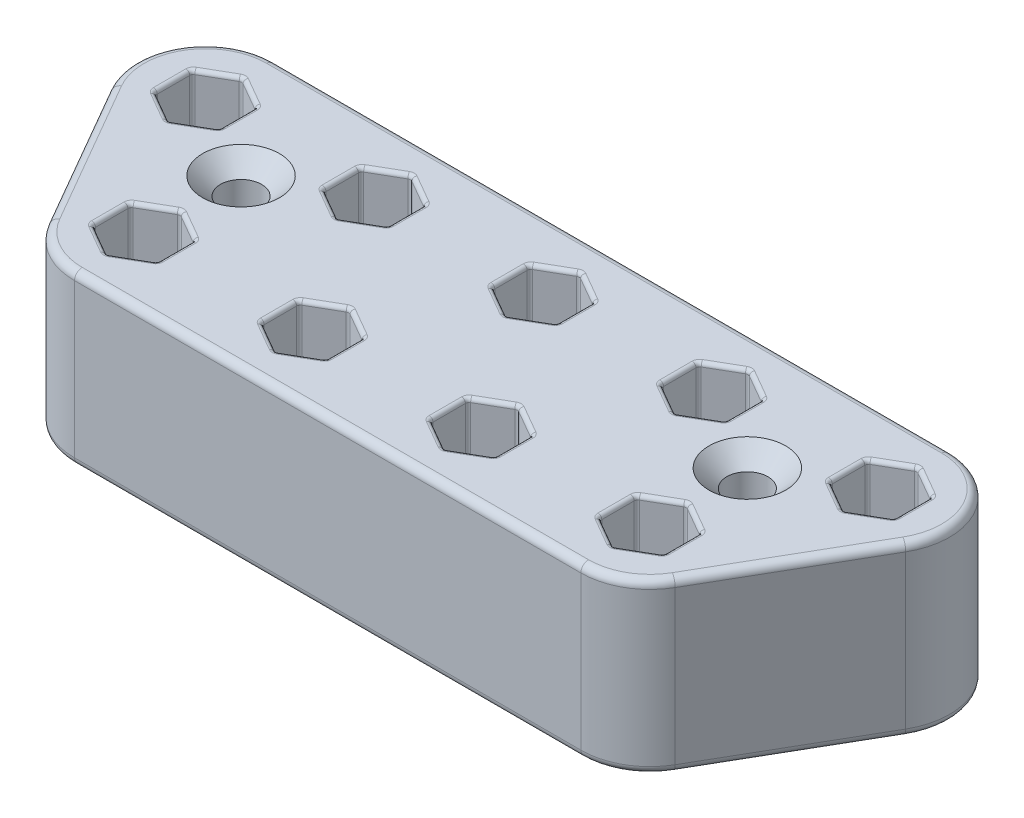
SolidWorks part; units mm, degrees
ref_plane "Front Plane" through (0, 0, 0) normal (0, 0, 1) x (1, 0, 0)
ref_plane "Top Plane" through (0, 0, 0) normal (0, 1, 0) x (1, 0, 0)
ref_plane "Right Plane" through (0, 0, 0) normal (1, 0, 0) x (0, 0, -1)
sketch "Sketch1" plane through (0, 0, 0) normal (0, 1, 0) x (1, 0, 0)
  line L1 (3.302, 1.9064) -> (0, 3.8128)
  line L2 (0, 3.8128) -> (-3.302, 1.9064)
  line L3 (-3.302, 1.9064) -> (-3.302, -1.9064)
  line L4 (-3.302, -1.9064) -> (0, -3.8128)
  line L5 (0, -3.8128) -> (3.302, -1.9064)
  line L6 (3.302, -1.9064) -> (3.302, 1.9064)
  line L7 (8.7313, 5.041) -> (0, 10.082)
  line L8 (0, 10.082) -> (-8.7312, 5.041)
  line L9 (-8.7312, 5.041) -> (-8.7312, -5.041)
  line L10 (-8.7312, -5.041) -> (0, -10.082)
  line L11 (0, -10.082) -> (8.7313, -5.041)
  line L12 (8.7313, -5.041) -> (8.7313, 5.041)
  circle A0 centre (0, 0) radius 3.302 construction
  circle A1 centre (0, 0) radius 8.7312 construction
  dimension "D2" = 17.4625
  dimension "D1" = 6.604
extrude "Boss-Extrude1" add sketch "Sketch1" along normal blind 15.875
sketch "Sketch3" plane through (0, 0, 0) normal (0, -1, 0) x (1, 0, 0)
  line L6 (8.7313, -5.041) -> (8.7313, 5.041)
  line L7 (8.7313, 5.041) -> (0, 10.082)
  line L8 (0, 10.082) -> (-8.7312, 5.041)
  line L9 (-8.7312, 5.041) -> (-8.7312, -5.041)
  line L10 (-8.7312, -5.041) -> (0, -10.082)
  line L11 (0, -10.082) -> (8.7313, -5.041)
  line L12 (8.7313, -5.041) -> (8.7313, 5.041)
  line L13 (8.7313, 5.041) -> (0, 10.082)
  line L14 (0, 10.082) -> (-8.7312, 5.041)
  line L15 (-8.7312, 5.041) -> (-8.7312, -5.041)
  line L16 (-8.7312, -5.041) -> (0, -10.082)
  line L17 (0, -10.082) -> (8.7313, -5.041)
  dimension "D1" = 0
extrude "Boss-Extrude3" add sketch "Sketch3" along normal blind 1.5875
fillet "Fillet1" radius 0.3969 18 edges at (0, 7.9375, 3.8128) (1.651, 0, 2.8596) (-1.651, 0, 2.8596) (-1.651, 15.875, 2.8596) (-3.302, 7.9375, 1.9064) (3.302, 7.9375, 1.9064) (1.651, 15.875, 2.8596) (3.302, 0, 0) (-3.302, 0, 0) (-3.302, 15.875, 0) (-3.302, 7.9375, -1.9064) (3.302, 7.9375, -1.9064) (3.302, 15.875, 0) (1.651, 0, -2.8596) (-1.651, 0, -2.8596) (-1.651, 15.875, -2.8596) (1.651, 15.875, -2.8596) (0, 7.9375, -3.8128)
pattern_linear "LPattern1" count 5 spacing 17.4625 along (1, 0, 0) count 2 spacing 17.4625 along (0.5, 0, 0.866) skipping (4, 1) of "Boss-Extrude1", "Boss-Extrude3", "Fillet1"
sketch "Sketch5" plane through (0, -1.5875, 0) normal (0, -1, 0) x (1, 0, 0)
  line L48 (0, 20.164) -> (0, 10.082)
  line L49 (0, 10.082) -> (-8.7312, 5.041)
  line L50 (-8.7312, 5.041) -> (-8.7312, -5.041)
  line L51 (-8.7312, -5.041) -> (0, -10.082)
  line L52 (0, -10.082) -> (8.7312, -5.041)
  line L53 (8.7312, -5.041) -> (17.4625, -10.082)
  line L54 (17.4625, -10.082) -> (26.1938, -5.041)
  line L55 (26.1938, -5.041) -> (34.925, -10.082)
  line L56 (34.925, -10.082) -> (43.6562, -5.041)
  line L57 (43.6562, -5.041) -> (52.3875, -10.082)
  line L58 (52.3875, -10.082) -> (61.1187, -5.041)
  line L59 (61.1187, -5.041) -> (69.85, -10.082)
  line L60 (69.85, -10.082) -> (78.5813, -5.041)
  line L61 (78.5813, -5.041) -> (78.5813, 5.041)
  line L62 (78.5813, 5.041) -> (69.85, 10.082)
  line L63 (69.85, 10.082) -> (69.85, 20.164)
  line L64 (69.85, 20.164) -> (61.1188, 25.2049)
  line L65 (61.1188, 25.2049) -> (52.3875, 20.164)
  line L66 (52.3875, 20.164) -> (43.6563, 25.2049)
  line L67 (43.6563, 25.2049) -> (34.925, 20.164)
  line L68 (34.925, 20.164) -> (26.1938, 25.2049)
  line L69 (26.1938, 25.2049) -> (17.4625, 20.164)
  line L70 (17.4625, 20.164) -> (8.7313, 25.2049)
  line L71 (8.7313, 25.2049) -> (0, 20.164)
  line L72 (0, 20.164) -> (0, 10.082)
  line L73 (0, 10.082) -> (-8.7312, 5.041)
  line L74 (-8.7312, 5.041) -> (-8.7312, -5.041)
  line L75 (-8.7312, -5.041) -> (0, -10.082)
  line L76 (0, -10.082) -> (8.7312, -5.041)
  line L77 (8.7312, -5.041) -> (17.4625, -10.082)
  line L78 (17.4625, -10.082) -> (26.1938, -5.041)
  line L79 (26.1938, -5.041) -> (34.925, -10.082)
  line L80 (34.925, -10.082) -> (43.6562, -5.041)
  line L81 (43.6562, -5.041) -> (52.3875, -10.082)
  line L82 (52.3875, -10.082) -> (61.1187, -5.041)
  line L83 (61.1187, -5.041) -> (69.85, -10.082)
  line L84 (69.85, -10.082) -> (78.5813, -5.041)
  line L85 (78.5813, -5.041) -> (78.5813, 5.041)
  line L86 (78.5813, 5.041) -> (69.85, 10.082)
  line L87 (69.85, 10.082) -> (69.85, 20.164)
  line L88 (69.85, 20.164) -> (61.1188, 25.2049)
  line L89 (61.1188, 25.2049) -> (52.3875, 20.164)
  line L90 (52.3875, 20.164) -> (43.6563, 25.2049)
  line L91 (43.6563, 25.2049) -> (34.925, 20.164)
  line L92 (34.925, 20.164) -> (26.1938, 25.2049)
  line L93 (26.1938, 25.2049) -> (17.4625, 20.164)
  line L94 (17.4625, 20.164) -> (8.7313, 25.2049)
  line L95 (8.7313, 25.2049) -> (0, 20.164)
  line L120 (-6.35, 23.8301) -> (-6.35, 13.7482)
  line L121 (-6.35, 13.7482) -> (-15.0812, 8.7072)
  line L122 (-15.0812, 8.7072) -> (-15.0812, -8.7072)
  line L123 (-15.0812, -8.7072) -> (0, -17.4143)
  line L124 (0, -17.4143) -> (8.7312, -12.3733)
  line L125 (8.7312, -12.3733) -> (17.4625, -17.4143)
  line L126 (17.4625, -17.4143) -> (26.1938, -12.3733)
  line L127 (26.1938, -12.3733) -> (34.925, -17.4143)
  line L128 (34.925, -17.4143) -> (43.6562, -12.3733)
  line L129 (43.6562, -12.3733) -> (52.3875, -17.4143)
  line L130 (52.3875, -17.4143) -> (61.1187, -12.3733)
  line L131 (61.1187, -12.3733) -> (69.85, -17.4143)
  line L132 (69.85, -17.4143) -> (84.9313, -8.7072)
  line L133 (84.9313, -8.7072) -> (84.9313, 8.7072)
  line L134 (84.9313, 8.7072) -> (76.2, 13.7482)
  line L135 (76.2, 13.7482) -> (76.2, 23.8301)
  line L136 (76.2, 23.8301) -> (61.1188, 32.5373)
  line L137 (61.1188, 32.5373) -> (52.3875, 27.4963)
  line L138 (52.3875, 27.4963) -> (43.6563, 32.5373)
  line L139 (43.6563, 32.5373) -> (34.925, 27.4963)
  line L140 (34.925, 27.4963) -> (26.1938, 32.5373)
  line L141 (26.1938, 32.5373) -> (17.4625, 27.4963)
  line L142 (17.4625, 27.4963) -> (8.7313, 32.5373)
  line L143 (8.7313, 32.5373) -> (-6.35, 23.8301)
  line L144 (-6.35, 23.8301) -> (-6.35, 13.7482)
  line L145 (-6.35, 13.7482) -> (-15.0812, 8.7072)
  line L146 (-15.0812, 8.7072) -> (-15.0812, -8.7072)
  line L147 (-15.0812, -8.7072) -> (0, -17.4143)
  line L148 (0, -17.4143) -> (8.7312, -12.3733)
  line L149 (8.7312, -12.3733) -> (17.4625, -17.4143)
  line L150 (17.4625, -17.4143) -> (26.1938, -12.3733)
  line L151 (26.1938, -12.3733) -> (34.925, -17.4143)
  line L152 (34.925, -17.4143) -> (43.6562, -12.3733)
  line L153 (43.6562, -12.3733) -> (52.3875, -17.4143)
  line L154 (52.3875, -17.4143) -> (61.1187, -12.3733)
  line L155 (61.1187, -12.3733) -> (69.85, -17.4143)
  line L156 (69.85, -17.4143) -> (84.9313, -8.7072)
  line L157 (84.9313, -8.7072) -> (84.9313, 8.7072)
  line L158 (84.9313, 8.7072) -> (76.2, 13.7482)
  line L159 (76.2, 13.7482) -> (76.2, 23.8301)
  line L160 (76.2, 23.8301) -> (61.1188, 32.5373)
  line L161 (61.1188, 32.5373) -> (52.3875, 27.4963)
  line L162 (52.3875, 27.4963) -> (43.6563, 32.5373)
  line L163 (43.6563, 32.5373) -> (34.925, 27.4963)
  line L164 (34.925, 27.4963) -> (26.1938, 32.5373)
  line L165 (26.1938, 32.5373) -> (17.4625, 27.4963)
  line L166 (17.4625, 27.4963) -> (8.7313, 32.5373)
  line L167 (8.7313, 32.5373) -> (-6.35, 23.8301)
  dimension "D1" = 0
  dimension "D2" = 6.35
extrude "Boss-Extrude4" add sketch "Sketch5" against normal up to surface (17.4625 mm away) up to face at (69.85, 15.875, 0)
sketch "Sketch4" plane through (0, 15.875, 0) normal (0, 1, 0) x (1, 0, 0)
  line L0 (0, 0) -> (8.7313, -15.123) construction
  line L1 (8.7313, -15.123) -> (61.1187, -15.123) construction
  line L2 (61.1187, -15.123) -> (69.85, 0) construction
  line L3 (69.85, 0) -> (0, 0) construction
  line L5 (-12.3733, 7.1437) -> (4.6068, -22.2667)
  line L6 (4.6068, -22.2667) -> (65.2432, -22.2667)
  line L7 (65.2432, -22.2667) -> (82.2233, 7.1437)
  line L8 (82.2233, 7.1437) -> (-12.3733, 7.1437)
  line L9 (-3.1036, 2.021) -> (-0.1984, 3.6983) construction
  point P3 (59.7318, -14.2324)
  dimension "D2" = 17.4625
  dimension "D1" = 69.85
  dimension "D3" = 7.1437
extrude "Cut-Extrude1" cut sketch "Sketch4" against normal through all both and the other way through all flip side to cut
fillet "Fillet2" radius 7.1437 4 edges at (82.2233, 7.1438, -7.1437) (65.2432, 7.1438, 22.2667) (4.6068, 7.1438, 22.2667) (-12.3733, 7.1437, -7.1437)
fillet "Fillet3" radius 0.7937 16 edges at (-1.821, -1.5875, 11.1334) (5.1594, -1.5875, 21.3096) (34.925, -1.5875, 22.2667) (64.6906, -1.5875, 21.3096) (71.671, -1.5875, 11.1334) (76.0367, -1.5875, -3.5719) (34.925, -1.5875, -7.1437) (34.925, 15.875, -7.1437) (76.0367, 15.875, -3.5719) (71.671, 15.875, 11.1334) (64.6906, 15.875, 21.3096) (34.925, 15.875, 22.2667) (5.1594, 15.875, 21.3096) (-1.821, 15.875, 11.1334) (-6.1867, -1.5875, -3.5719) (-6.1867, 15.875, -3.5719)
sketch "Sketch6" plane through (0, 0, 0) normal (0, 1, 0) x (1, 0, 0)
  circle A0 centre (8.7312, -5.041) radius 6.7274 construction
  point P11 (8.7312, -5.041)
ref_axis "Axis1" through (8.7312, 0, 5.041) along (0, 1, 0)
ref_plane "Plane1" through (8.7312, 0, 0) normal (1, 0, 0) x (0, 1, 0)
sketch "Sketch7" plane through (8.7312, 0, 0) normal (1, 0, 0) x (0, 1, 0)
  line L0 (-1.5875, 5.041) -> (-1.5875, 7.1682)
  line L1 (0, 5.041) -> (32.3541, 5.041) construction
  line L2 (-1.5875, 7.1682) -> (14.0335, 7.1682)
  line L3 (14.0335, 7.1682) -> (15.875, 9.0097)
  line L4 (15.875, 9.0097) -> (15.875, 5.041)
  line L5 (15.875, 5.041) -> (-1.5875, 5.041) construction
  line L6 (15.875, 3.175) -> (15.875, 18.298) construction
  line L7 (-1.5875, 21.473) -> (-1.5875, 18.298) construction
  line L8 (-1.5875, 5.041) -> (15.875, 5.041)
  dimension "D1" = 4.2545
  dimension "D2" = 7.9375
  dimension "D3" = 45
revolve "Cut-Revolve1" cut sketch "Sketch7" angle 360 about L5
ref_plane "Plane2" through (34.925, 0, 0) normal (-1, 0, 0) x (0, 0, 1)
mirror "Mirror2" about plane through (34.925, 0, 0) normal (-1, 0, 0) of "Cut-Revolve1"
equation "\"hex_width\"= 0.6875in"
equation "\"D2@Sketch1\"=\"hex_width\""
equation "\"D3@LPattern1\"=\"hex_width\""
equation "\"D4@LPattern1\"=\"hex_width\""
equation "\"num_wide\"= 5"
equation "\"D1@LPattern1\"=\"num_wide\""
equation "\"D1@Sketch4\"=\"hex_width\"*(\"num_wide\"-1)"
equation "\"D2@Sketch4\"=\"hex_width\""
equation "\"offset\"=0.28125"
equation "\"D3@Sketch4\"=\"offset\""
equation "\"D1@Fillet2\"=\"offset\""
